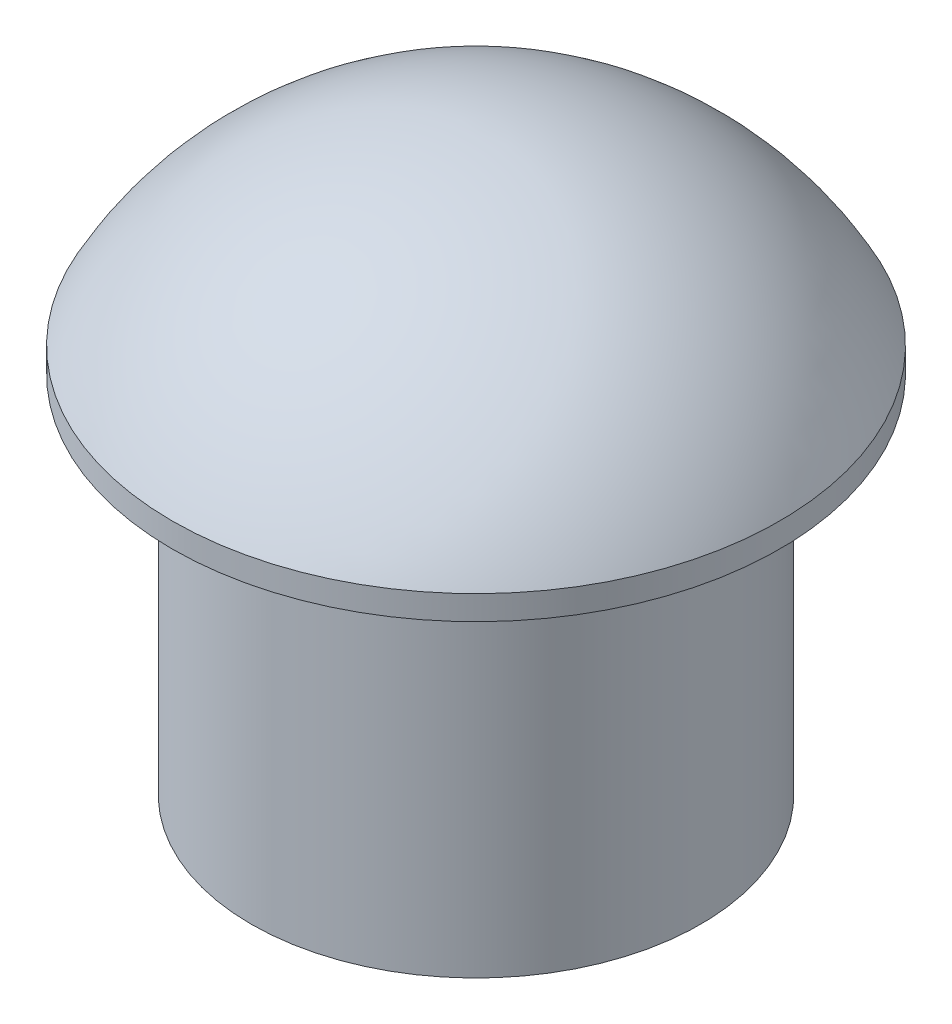
SolidWorks part; units mm, degrees
ref_plane "Front Plane" through (0, 0, 0) normal (0, 0, 1) x (1, 0, 0)
ref_plane "Top Plane" through (0, 0, 0) normal (0, 1, 0) x (1, 0, 0)
ref_plane "Right Plane" through (0, 0, 0) normal (1, 0, 0) x (0, 0, -1)
sketch "Sketch1" plane through (0, 0, 0) normal (0, 1, 0) x (1, 0, 0)
  circle A0 centre (0, 0) radius 1.85
  dimension "D1" = 3.7
extrude "Boss-Extrude1" add sketch "Sketch1" along normal blind 3
sketch "Sketch2" plane through (0, 3, 0) normal (0, 1, 0) x (1, 0, 0)
  circle A0 centre (0, 0) radius 2.5
  dimension "D1" = 5
extrude "Boss-Extrude2" add sketch "Sketch2" along normal blind 0.2
dome "Dome2" faces to dome 1 distance 1.5 reverse direction no elliptical dome no face at (0, 3.2, 2.5) parameters "D1"=1.5
